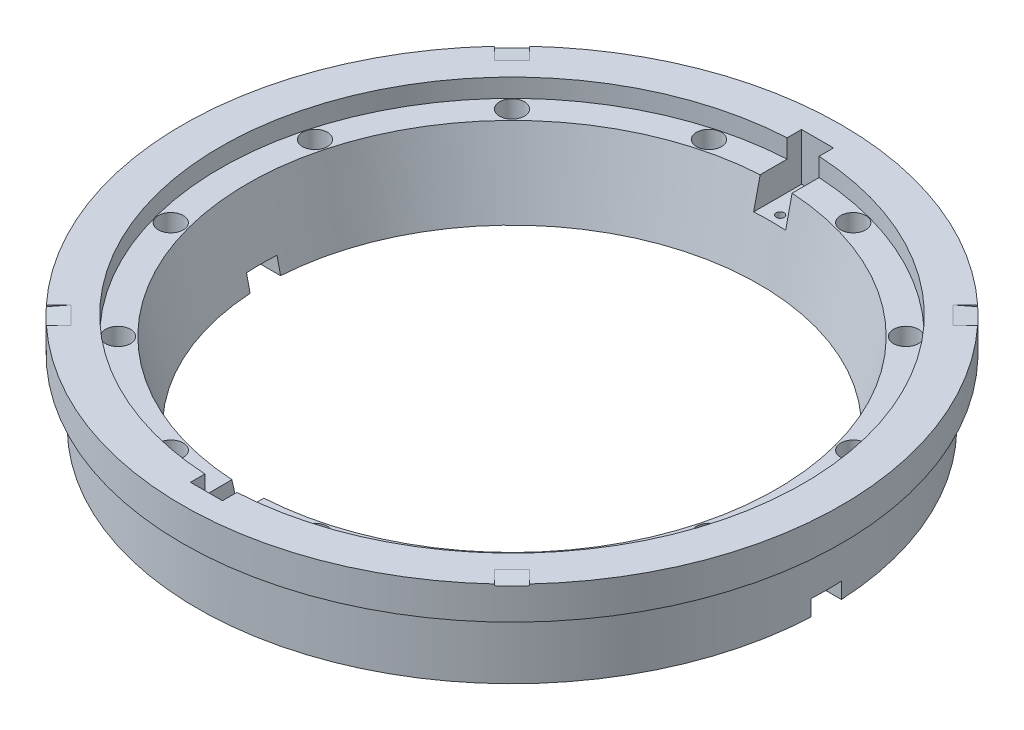
SolidWorks part; units mm, degrees
ref_plane "前视基准面" through (0, 0, 0) normal (0, 0, 1) x (1, 0, 0)
ref_plane "上视基准面" through (0, 0, 0) normal (0, 1, 0) x (1, 0, 0)
ref_plane "右视基准面" through (0, 0, 0) normal (1, 0, 0) x (0, 0, -1)
sketch "草图1" plane through (0, 0, 0) normal (0, 0, 1) x (1, 0, 0)
  line L8 (0, 0) -> (0, 290.3832) construction
  line L9 (-330, 0) -> (-292, 0)
  line L10 (-292, 0) -> (-292, -18.5)
  line L11 (-292, -18.5) -> (-265, -18.5)
  line L12 (-265, -18.5) -> (-247.5, -97)
  line L13 (-247.5, -97) -> (-315, -97)
  line L14 (-315, -97) -> (-315, -37.02)
  line L15 (-315, -37.02) -> (-330, -33)
  line L16 (-330, -33) -> (-330, 0)
  dimension "D1" = 584
  dimension "D2" = 530
  dimension "D3" = 495
  dimension "D4" = 18.5
  dimension "D5" = 97
  dimension "D6" = 33
  dimension "D7" = 37.02
  dimension "D8" = 630
  dimension "D9" = 660
revolve "旋转1" add sketch "草图1" angle 360 about L8
sketch "草图2" plane through (0, -18.5, 0) normal (0, 1, 0) x (1, 0, 0)
  circle A0 centre (0, 0) radius 279 construction
  circle A1 centre (-72.2105, 269.4933) radius 8.5
  circle A2 centre (72.2105, 269.4933) radius 8.5
  circle A3 centre (197.2828, 197.2828) radius 8.5
  circle A4 centre (269.4933, 72.2105) radius 8.5
  circle A5 centre (269.4933, -72.2105) radius 8.5
  circle A6 centre (197.2828, -197.2828) radius 8.5
  circle A7 centre (72.2105, -269.4933) radius 8.5
  circle A8 centre (-72.2105, -269.4933) radius 8.5
  circle A9 centre (-197.2828, -197.2828) radius 8.5
  circle A10 centre (-269.4933, -72.2105) radius 8.5
  circle A11 centre (-269.4933, 72.2105) radius 8.5
  circle A12 centre (-197.2828, 197.2828) radius 8.5
  point P30 (0, 0)
  dimension "D1" = 558
  dimension "D2" = 17
  dimension "D3" = 12
extrude "切除-拉伸1" cut sketch "草图2" against normal up to next
sketch "草图3" plane through (0, -18.5, 0) normal (0, 1, 0) x (1, 0, 0)
  circle A0 centre (-72.2105, 269.4933) radius 12.5
  circle A1 centre (72.2105, 269.4933) radius 12.5
  circle A2 centre (197.2828, 197.2828) radius 12.5
  circle A3 centre (269.4933, 72.2105) radius 12.5
  circle A4 centre (269.4933, -72.2105) radius 12.5
  circle A5 centre (197.2828, -197.2828) radius 12.5
  circle A6 centre (72.2105, -269.4933) radius 12.5
  circle A7 centre (-72.2105, -269.4933) radius 12.5
  circle A8 centre (-197.2828, -197.2828) radius 12.5
  circle A9 centre (-269.4933, -72.2105) radius 12.5
  circle A10 centre (-269.4933, 72.2105) radius 12.5
  circle A11 centre (-197.2828, 197.2828) radius 12.5
  point P27 (0, 0)
  dimension "D1" = 25
  dimension "D2" = 12
extrude "切除-拉伸2" cut sketch "草图3" against normal blind 18
sketch "草图4" plane through (0, 0, 0) normal (0, 1, 0) x (1, 0, 0)
  line L0 (-16, 256.5) -> (-16, 306)
  line L1 (-16, 306) -> (16, 306)
  line L2 (16, 306) -> (16, 256.5)
  line L3 (16, 256.5) -> (-16, 256.5)
  line L4 (0, 0) -> (0, 157.7201) construction
  line L5 (0, 0) -> (146.3737, 0) construction
  line L6 (16, -256.5) -> (-16, -256.5)
  line L7 (16, -306) -> (16, -256.5)
  line L8 (-16, -306) -> (16, -306)
  line L9 (-16, -256.5) -> (-16, -306)
  dimension "D1" = 32
  dimension "D2" = 612
  dimension "D3" = 513
extrude "切除-拉伸3" cut sketch "草图4" against normal blind 47.5
sketch "草图7" plane through (0, -47.5, 0) normal (0, 1, 0) x (1, 0, 0)
  line L0 (0, 0) -> (0, 355.6286) construction
  line L1 (-16, 282.0197) -> (16, 282.0197) construction
  line L2 (-16, 306) -> (-16, 258.0395) construction
  line L3 (16, 258.0395) -> (16, 306) construction
  line L4 (0, 0) -> (176.8564, 0) construction
  circle A0 centre (0, 295.5197) radius 4
  circle A1 centre (0, 268.5197) radius 4
  circle A2 centre (0, -268.5197) radius 4
  circle A3 centre (0, -295.5197) radius 4
  dimension "D1" = 8
  dimension "D2" = 27
extrude "切除-拉伸4" cut sketch "草图7" against normal up to next
sketch "草图8" plane through (0, -97, 0) normal (0, -1, 0) x (1, 0, 0)
  line L0 (548.7916, 0) -> (-439.5618, 0) construction
  line L1 (0, 438.2581) -> (0, -449.6744) construction
  line L2 (351, 15.25) -> (351, -15.25)
  line L3 (-351, 15.25) -> (-220, 15.25)
  line L4 (-351, 15.25) -> (-351, -15.25)
  line L5 (-351, -15.25) -> (-220, -15.25)
  line L6 (-220, 15.25) -> (-220, -15.25)
  line L7 (351, -15.25) -> (220, -15.25)
  line L8 (220, 15.25) -> (220, -15.25)
  line L9 (351, 15.25) -> (220, 15.25)
  dimension "D1" = 30.5
  dimension "D2" = 220
  dimension "D3" = 131
extrude "切除-拉伸5" cut sketch "草图8" against normal blind 16
sketch "草图9" plane through (0, 0, 0) normal (0, 1, 0) x (1, 0, 0)
  line L0 (0, 409.5243) -> (0, -369.7909) construction
  line L1 (-448.0314, 0) -> (480.9602, 0) construction
  line L2 (-237.834, 255.5117) -> (-255.5117, 237.834)
  line L3 (-312.1525, 12.5) -> (-348.8481, 12.5)
  line L4 (-312.1525, 12.5) -> (-312.1525, -12.5)
  line L5 (-312.1525, -12.5) -> (-348.8481, -12.5)
  line L6 (-348.8481, 12.5) -> (-348.8481, -12.5)
  line L7 (-211.8863, 229.564) -> (-237.834, 255.5117)
  line L8 (-211.8863, 229.564) -> (-229.564, 211.8863)
  line L9 (-229.564, 211.8863) -> (-255.5117, 237.834)
  line L10 (255.5117, 237.834) -> (237.834, 255.5117)
  line L11 (229.564, 211.8863) -> (255.5117, 237.834)
  line L12 (229.564, 211.8863) -> (211.8863, 229.564)
  line L13 (211.8863, 229.564) -> (237.834, 255.5117)
  line L14 (237.834, -255.5117) -> (255.5117, -237.834)
  line L15 (211.8863, -229.564) -> (237.834, -255.5117)
  line L16 (211.8863, -229.564) -> (229.564, -211.8863)
  line L17 (229.564, -211.8863) -> (255.5117, -237.834)
  line L18 (-255.5117, -237.834) -> (-237.834, -255.5117)
  line L19 (-229.564, -211.8863) -> (-255.5117, -237.834)
  line L20 (-229.564, -211.8863) -> (-211.8863, -229.564)
  line L21 (-211.8863, -229.564) -> (-237.834, -255.5117)
  circle A0 centre (0, 0) radius 315 construction
  point P12 (-220.7252, 220.7252)
  point P17 (0, 0)
  point P30 (0, 0)
  dimension "D1" = 630
  dimension "D2" = 25
  dimension "D3" = 36.6956
  dimension "D4" = 312.1525
  dimension "D5" = 2
  dimension "D6" = 4
revolve "切除-旋转1" cut sketch "草图9" angle 5 about L8
revolve "切除-旋转3" cut sketch "草图9<3>" angle 5 about L12
sketch "草图9<3>" plane through (0, 0, 0) normal (0, 1, 0) x (1, 0, 0) same geometry as "草图9"
revolve "切除-旋转4" cut sketch "草图9<4>" angle 5 about L16
sketch "草图9<4>" plane through (0, 0, 0) normal (0, 1, 0) x (1, 0, 0) same geometry as "草图9"
revolve "切除-旋转5" cut sketch "草图9<5>" angle 5 about L20
sketch "草图9<5>" plane through (0, 0, 0) normal (0, 1, 0) x (1, 0, 0) same geometry as "草图9"
